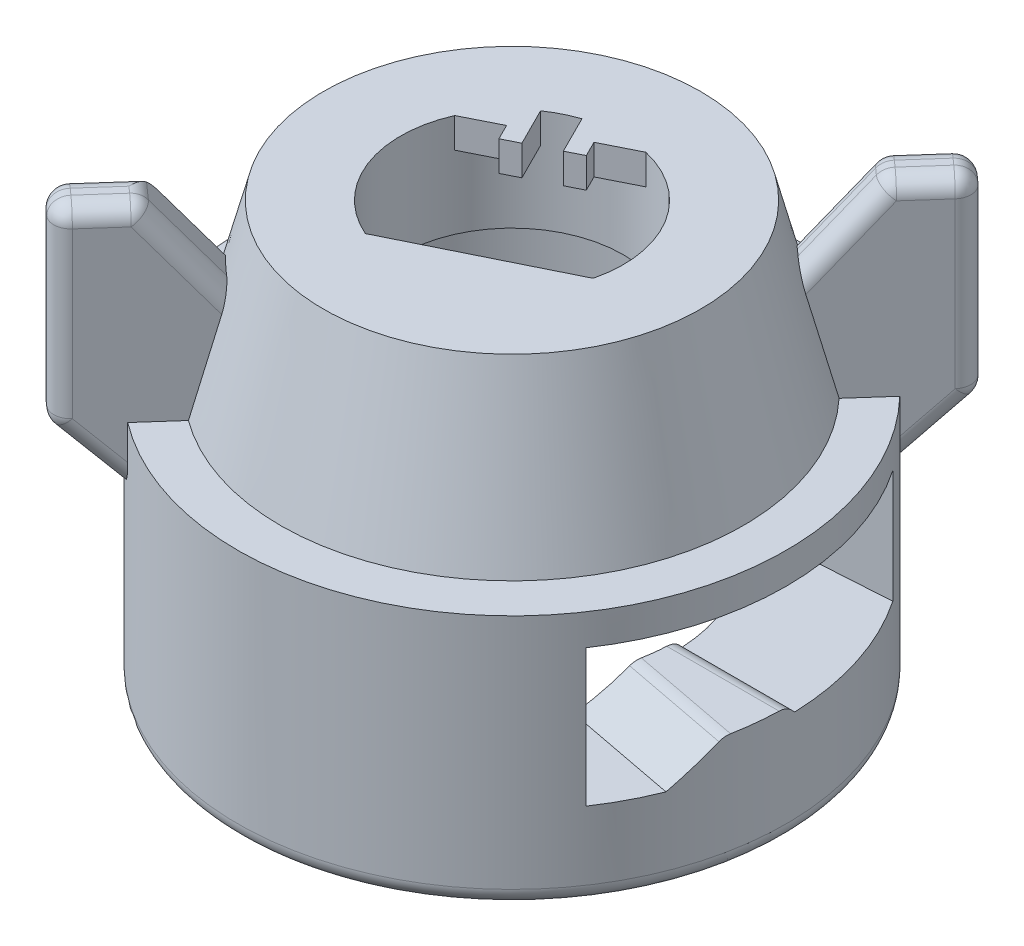
SolidWorks part; units mm, degrees
ref_plane "Front Plane" through (0, 0, 0) normal (0, 0, 1) x (1, 0, 0)
ref_plane "Top Plane" through (0, 0, 0) normal (0, 1, 0) x (1, 0, 0)
ref_plane "Right Plane" through (0, 0, 0) normal (1, 0, 0) x (0, 0, -1)
sketch "Croquis1" plane through (0, 0, 0) normal (0, 0, 1) x (1, 0, 0)
  line L0 (0, 0) -> (0, 24.5) construction
  line L1 (6.5, 24.5) -> (11, 24.5)
  line L2 (11, 24.5) -> (13.5, 14.8175)
  line L3 (13.5, 14.8175) -> (16, 14.8175)
  line L4 (16, 14.8175) -> (16, 0)
  line L5 (16, 0) -> (13.85, 0)
  line L6 (13.85, 0) -> (13.85, 1.5)
  line L7 (13.85, 1.5) -> (9.45, 1.5)
  line L8 (9.45, 1.5) -> (9.45, 16.7)
  line L9 (9.45, 16.7) -> (6.5, 18.5)
  line L10 (6.5, 18.5) -> (6.5, 24.5)
  dimension "D1" = 24.5
  dimension "D2" = 6
  dimension "D3" = 17
  dimension "D4" = 6.5
  dimension "D5" = 2.15
  dimension "D6" = 16
  dimension "D7" = 10
  dimension "D8" = 2.5
  dimension "D9" = 4.5
  dimension "D10" = 15.2
  dimension "D11" = 4.4
revolve "Revolución1" add sketch "Croquis1" angle 360 about L0
ref_plane "Plano1" through (0, 5, 0) normal (0, 1, 0) x (1, 0, 0)
sketch "Croquis3" plane through (0, 5, 0) normal (0, 1, 0) x (1, 0, 0)
  line L0 (13.2626, -8.95) -> (-13.2626, 8.95) construction
  line L1 (13.2626, 8.95) -> (-13.2626, -8.95) construction
  line L2 (13.2626, 8.95) -> (9.3103, 8.7)
  line L3 (9.3103, 8.7) -> (5.4784, 7.7)
  line L4 (5.4784, 7.7) -> (5.4784, -7.7) construction
  line L6 (-13.2626, -8.95) -> (-9.3103, -8.7)
  line L7 (-9.3103, -8.7) -> (-5.4784, -7.7)
  line L17 (-13.2626, 8.95) -> (-10.2826, 8.95)
  line L19 (-9.4535, 7.7) -> (-5.4784, 7.7)
  line L20 (-10.2826, 8.95) -> (-9.4535, 7.7)
  line L21 (5.4784, -7.7) -> (9.4535, -7.7)
  line L22 (9.4535, -7.7) -> (10.2826, -8.95)
  line L23 (10.2826, -8.95) -> (13.2626, -8.95)
  arc A0 (-5.4784, 7.7) -> (-5.4784, -7.7) centre (0, 0) ccw
  circle A1 centre (0, 0) radius 9.45 construction
  circle A2 centre (0, 0) radius 16 construction
  arc A3 (-13.2626, 8.95) -> (-13.2626, -8.95) centre (0, 0) ccw
  arc A4 (5.4784, -7.7) -> (5.4784, 7.7) centre (0, 0) ccw
  arc A5 (13.2626, -8.95) -> (13.2626, 8.95) centre (0, 0) ccw
  point P9 (0, 0)
  point P13 (0, 0)
  point P20 (5.4784, 0)
  dimension "D1" = 17.9
  dimension "D2" = 15.4
  dimension "D3" = 1
  dimension "D4" = 2.98
  dimension "D5" = 15.4
  dimension "D6" = 1
  dimension "D9" = 1.5
extrude "Cortar-Extruir1" cut sketch "Croquis3" along normal blind 8
ref_plane "Plano2" through (0, 1.5, 0) normal (0, -1, 0) x (-1, 0, 0)
sketch "Croquis5" plane through (0, 1.5, 0) normal (0, -1, 0) x (-1, 0, 0)
  line L0 (-9.4535, -7.7) -> (4.1537, 11.4632)
  line L2 (9.4535, 7.7) -> (-4.1537, -11.4632)
  arc A0 (-9.4535, -7.7) -> (-4.1537, -11.4632) centre (0, 0) ccw
  arc A1 (9.4535, 7.7) -> (4.1537, 11.4632) centre (0, 0) ccw
  dimension "D1" = 6.5
extrude "Cortar-Extruir2" cut sketch "Croquis5" against normal up to surface (11.5 mm away) up to face at (-10.4625, 13, -1.1357)
sketch "Croquis6" plane through (0, 5, 0) normal (0, 1, 0) x (1, 0, 0)
  line L0 (5.4784, 7.7) -> (9.3103, 8.7)
  line L1 (13.2626, 8.95) -> (9.3103, 8.7) construction
  line L2 (9.3103, 8.7) -> (13.2626, 8.95)
  line L3 (9.45, 0) -> (16, 0)
  line L4 (-9.45, 0) -> (-16, 0)
  line L5 (-13.2626, -8.95) -> (-9.3103, -8.7)
  line L6 (-9.3103, -8.7) -> (-5.4784, -7.7)
  arc A0 (-9.45, 0) -> (-5.4784, -7.7) centre (0, 0) ccw
  arc A1 (-16, 0) -> (-13.2626, -8.95) centre (0, 0) ccw
  arc A2 (7.7873, -5.3535) -> (-2.4875, 9.1167) centre (0, 0) ccw construction
  circle A3 centre (0, 0) radius 16 construction
  arc A4 (9.45, 0) -> (5.4784, 7.7) centre (0, 0) ccw
  arc A5 (16, 0) -> (13.2626, 8.95) centre (0, 0) ccw
extrude "Saliente-Extruir1" add sketch "Croquis6" along normal blind 1.4
sketch "Croquis7" plane through (0, 6.4, 0) normal (0, 1, 0) x (1, 0, 0)
  line L0 (9.45, 0) -> (16, 0)
  line L1 (-9.45, 0) -> (-16, 0)
  line L2 (-9.2824, 1.7719) -> (-15.7162, 3)
  line L3 (9.2824, -1.7719) -> (15.7162, -3)
  line L4 (9.2824, -1.7719) -> (9.45, 0) construction
  line L5 (-9.45, 0) -> (-9.2824, 1.7719) construction
  circle A0 centre (0, 0) radius 9.45
  arc A1 (7.7873, -5.3535) -> (-2.4875, 9.1167) centre (0, 0) ccw construction
  circle A2 centre (0, 0) radius 16
  circle A3 centre (0, 0) radius 16 construction
  line M6 (9.45, 0) -> (16, 0)
  dimension "D1" = 3
extrude "Saliente-Extruir2" add sketch "Croquis7" along normal blind 0.5 and the other way blind 1.4 contours L2 A2 L1 A0 | L3 A2 A0 M6 region at (12.929, 6.4, 1.2229) region at (-12.929, 6.4, -1.2229)
chamfer "Chaflán1" distance 0.5 angle 45 2 edges at (-12.725, 6.4, 0) (12.725, 6.4, 0)
chamfer "Chaflán2" distance 3 angle 35 1 edges at (-12.4993, 5, -2.3859) first distance on face at (-11.0455, 5, -5.9879)
chamfer "Chaflán3" distance 3 angle 35 1 edges at (12.4993, 5, 2.3859) first distance on face at (11.0455, 5, 5.9879)
fillet "Redondeo1" radius 1 4 edges at (-12.725, 6.9, 0) (-12.4422, 6.9, -2.6667) (12.725, 6.9, 0) (12.4422, 6.9, 2.6667)
fillet "Redondeo2" radius 1 2 edges at (0, 0, -16) (0, 0, -13.85)
sketch "Croquis8" plane through (0, 5, 0) normal (0, 1, 0) x (1, 0, 0)
  line L0 (-10.6282, -11.96) -> (0, 0) construction
  line L1 (0, 0) -> (2.4023, -2.1348) construction
  circle A1 centre (0, 0) radius 16 construction
  dimension "D1" = 4
ref_plane "Plano3" through (0, 5, 0) normal (0.7475, 0, 0.6643) x (0.6643, 0, -0.7475)
sketch "Croquis9" plane through (0, 5, 0) normal (0.7475, 0, 0.6643) x (0.6643, 0, -0.7475)
  line L0 (0, 0) -> (16, 0) construction
  line L1 (-16, 0) -> (0, 0) construction
  line L2 (17.6, 0) -> (-17.6, 0) construction
  line L3 (16, -4) -> (16, 9.8175) construction
  line L4 (16, 0) -> (16, 6.4278) construction
  line L5 (16, 6.4278) -> (19.2394, 9.6937)
  line L6 (19.2394, 9.6937) -> (19.2394, 20.6937)
  line L7 (19.2394, 20.6937) -> (15.3394, 20.6937)
  line L8 (15.3394, 20.6937) -> (10.9353, 15.308)
  line L9 (10.9353, 15.308) -> (12.7031, 9.8175)
  line L10 (16, 9.8175) -> (-16, 9.8175) construction
  line L11 (12.7031, 9.8175) -> (15.1469, 9.8175)
  line L12 (15.1469, 9.8175) -> (15.1469, 6.4278)
  line L13 (15.1469, 6.4278) -> (16, 6.4278)
  line L14 (13.5, 9.8175) -> (11, 19.5) construction
  line L15 (0, 0) -> (0, 13.1521) construction
  line L16 (-16, 6.4278) -> (-19.2394, 9.6937)
  line L17 (-15.1469, 6.4278) -> (-16, 6.4278)
  line L18 (-15.1469, 9.8175) -> (-15.1469, 6.4278)
  line L19 (-12.7031, 9.8175) -> (-15.1469, 9.8175)
  line L20 (-10.9353, 15.308) -> (-12.7031, 9.8175)
  line L21 (-15.3394, 20.6937) -> (-10.9353, 15.308)
  line L22 (-19.2394, 20.6937) -> (-15.3394, 20.6937)
  line L23 (-19.2394, 9.6937) -> (-19.2394, 20.6937)
  dimension "D1" = 11
  dimension "D2" = 4.6
  dimension "D3" = 4.5
  dimension "D4" = 3.9
extrude "Saliente-Extruir3" add sketch "Croquis9" along normal mid plane 2.5
fillet "Redondeo3" radius 1 21 edges at (9.9339, 23.5031, -9.2968) (12.4191, 25.6937, -12.0934) (13.7144, 20.1937, -13.551) (12.6385, 13.0608, -12.3403) (10.7697, 13.0608, -14.001) (11.8456, 20.1937, -15.2117) (10.5503, 25.6937, -13.7541) (8.0651, 23.5031, -10.9575) (-12.4191, 25.6937, 12.0934) (-13.7144, 20.1937, 13.551) (-12.6385, 13.0608, 12.3403) (-10.7697, 13.0608, 14.001) (-11.8456, 20.1937, 15.2117) (-8.0651, 23.5031, 10.9575) (-10.5503, 25.6937, 13.7541) (12.78, 14.6937, -14.3814) (12.78, 25.6937, -14.3814) (10.1894, 25.6937, -11.4661) (-12.78, 14.6937, 14.3814) (-10.1894, 25.6937, 11.4661) (-12.78, 25.6937, 14.3814)
sketch "Croquis10" plane through (0, 24.5, 0) normal (0, 1, 0) x (1, 0, 0)
  line L0 (0, 0) -> (2.8716, -5.8313) construction
  line L1 (2.8716, -5.8313) -> (-1.614, -8.0402)
  line L2 (-1.614, -8.0402) -> (-2.6301, -5.977)
  line L3 (-2.6301, -5.977) -> (6.3412, -1.5591)
  line L4 (6.3412, -1.5591) -> (7.3572, -3.6224)
  line L5 (7.3572, -3.6224) -> (2.8716, -5.8313)
  line L6 (0, 0) -> (-2.9101, 5.8122) construction
  line L7 (-10.6282, -11.96) -> (0, 0) construction
  line L8 (-2.1054, 6.2151) -> (-3.7149, 5.4092)
  line L9 (-3.7149, 5.4092) -> (-2.5956, 3.1738)
  line L10 (-2.5956, 3.1738) -> (-3.4898, 2.7261)
  line L11 (-3.4898, 2.7261) -> (-3.9375, 3.6202)
  line L12 (-3.9375, 3.6202) -> (-5.9524, 2.6114)
  line L13 (-5.9524, 2.6114) -> (-6.9379, 4.5622)
  line L14 (-0.0919, 4.4274) -> (-0.5396, 5.3215)
  line L15 (-2.1054, 6.2151) -> (-0.9861, 3.9797)
  line L16 (-0.9861, 3.9797) -> (-0.0919, 4.4274)
  line L17 (-0.5396, 5.3215) -> (1.4753, 6.3304)
  line L18 (1.4753, 6.3304) -> (0.5038, 8.2883)
  line L19 (-6.9379, 4.5622) -> (0.5038, 8.2883)
  circle A0 centre (0, 0) radius 6.5 construction
  dimension "D1" = 111.777
  dimension "D2" = 10.7
  dimension "D3" = 10
  dimension "D4" = 1
  dimension "D5" = 1.8
  dimension "D6" = 2.5
  dimension "D7" = 1
extrude "Saliente-Extruir4" add sketch "Croquis10" against normal blind 1.75
ref_plane "Plano4" through (0, 16.7, 0) normal (0, -1, 0) x (-1, 0, 0)
sketch "Croquis11" plane through (0, 16.7, 0) normal (0, -1, 0) x (-1, 0, 0)
  circle A0 centre (0, 0) radius 9.45
extrude "Cortar-Extruir3" cut sketch "Croquis11" against normal blind 1.8
